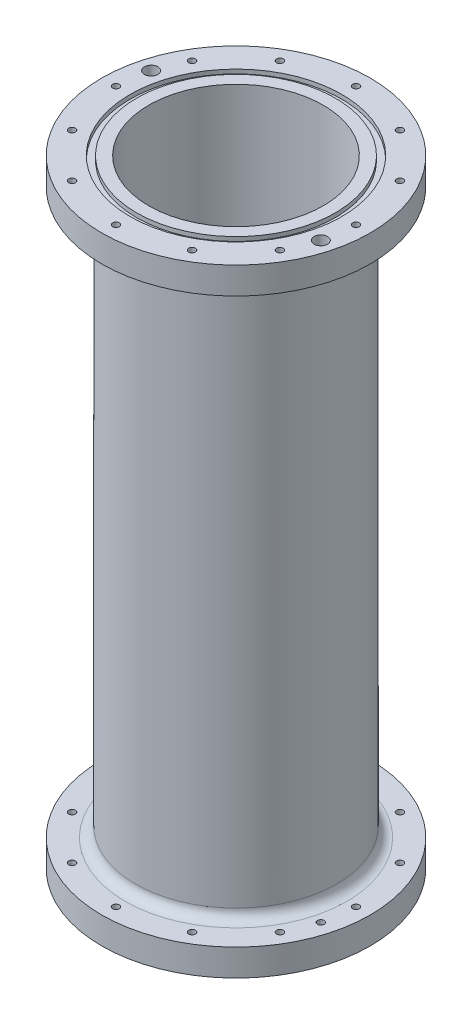
SolidWorks part; units mm, degrees
ref_plane "Front Plane" through (0, 0, 0) normal (0, 0, 1) x (1, 0, 0)
ref_plane "Top Plane" through (0, 0, 0) normal (0, 1, 0) x (1, 0, 0)
ref_plane "Right Plane" through (0, 0, 0) normal (1, 0, 0) x (0, 0, -1)
sketch "Sketch2" plane through (0, 0, 0) normal (0, 1, 0) x (1, 0, 0)
  circle A0 centre (0, 0) radius 41.275
  circle A1 centre (0, 0) radius 47.625
  dimension "D1" = 95.25
  dimension "D2" = 82.55
extrude "Base Cylinder" add sketch "Sketch2" along normal blind 292.1
sketch "Sketch3" plane through (0, 0, 0) normal (0, -1, 0) x (1, 0, 0)
  circle A0 centre (0, 0) radius 41.275
  circle A1 centre (0, 0) radius 63.5
  dimension "D1" = 127
extrude "Aft Flange" add sketch "Sketch3" against normal blind 12.7
sketch "Sketch4" plane through (0, 292.1, 0) normal (0, 1, 0) x (1, 0, 0)
  circle A0 centre (0, 0) radius 41.275
  circle A1 centre (0, 0) radius 63.5
  dimension "D1" = 127
extrude "Forward Flange" add sketch "Sketch4" against normal blind 12.7
sketch "Sketch6" plane through (0, 0, 0) normal (0, -1, 0) x (1, 0, 0)
  circle A0 centre (0, 0) radius 50.0761
  circle A1 centre (0, 0) radius 47.0027
  dimension "D1" = 100.1522
  dimension "D2" = 94.0054
extrude "Aft O-Ring" cut sketch "Sketch6" against normal blind 1.9812
sketch "Sketch7" plane through (0, 292.1, 0) normal (0, 1, 0) x (1, 0, 0)
  circle A0 centre (0, 0) radius 50.0761
  circle A1 centre (0, 0) radius 47.0027
  dimension "D1" = 100.1522
  dimension "D2" = 94.0054
extrude "Forward O-Ring" cut sketch "Sketch7" against normal blind 1.9812
sketch "Sketch For Bolt Holes" plane through (0, 0, 0) normal (0, -1, 0) x (1, 0, 0)
  circle A0 centre (-56.769, 0) radius 1.5875
  circle A1 centre (-49.1634, 28.3845) radius 1.5875
  circle A2 centre (-28.3845, 49.1634) radius 1.5875
  circle A3 centre (0, 56.769) radius 1.5875
  circle A4 centre (28.3845, 49.1634) radius 1.5875
  circle A5 centre (49.1634, 28.3845) radius 1.5875
  circle A6 centre (56.769, 0) radius 1.5875
  circle A7 centre (49.1634, -28.3845) radius 1.5875
  circle A8 centre (28.3845, -49.1634) radius 1.5875
  circle A9 centre (0, -56.769) radius 1.5875
  circle A10 centre (-28.3845, -49.1634) radius 1.5875
  circle A11 centre (-49.1634, -28.3845) radius 1.5875
  point P36 (0, 0)
  dimension "D2" = 3.175
  dimension "D1" = 56.769
  dimension "D3" = 12
hole_wizard "1/8 (0.125) Diameter Hole2" positions "Sketch8" profile "Sketch9" hole size "1/8" standard "ANSI Inch"
sketch "Sketch8" plane through (0, 0, 0) normal (0, -1, 0) x (-1, 0, 0)
  point P0 (-28.3845, -49.1634)
  point P3 (-49.1634, -28.3845)
  point P6 (-56.769, 0)
  point P9 (-49.1634, 28.3845)
  point P12 (-28.3845, 49.1634)
  point P15 (0, 56.769)
  point P18 (28.3845, 49.1634)
  point P21 (49.1634, 28.3845)
  point P24 (56.769, 0)
  point P27 (49.1634, -28.3845)
  point P30 (28.3845, -49.1634)
  point P33 (0, -56.769)
  point P36 (-28.3845, -49.1634)
  point P38 (-49.1634, -28.3845)
  point P40 (-56.769, 0)
sketch "Sketch9" plane through (28.3845, 0, 49.1634) normal (1, 0, 0) x (0, 0, -1)
  line L0 (0, 0) -> (0, 26.3539)
  line L1 (0, 26.3539) -> (1.5875, 25.4)
  line L2 (1.5875, 25.4) -> (1.5875, 0)
  line L5 (1.5875, 0) -> (0, 0)
  line L10 (0, 26.3539) -> (-1.5875, 25.4) construction
  line L11 (0, -6.35) -> (0, 107.95) construction
  dimension "Hole Dia." = 3.175
  dimension "Hole Depth" = 25.4
  dimension "Drill Angle" = 118
fillet "Flange Fillet" radius 4.7625 2 edges at (0, 12.7, -47.625) (0, 279.4, 47.625)
sketch "Dowel Hole Sketch" plane through (0, 0, 0) normal (0, -1, 0) x (1, 0, 0)
  line L0 (0, 0) -> (-56.769, 0) construction
  line L1 (0, 0) -> (-54.8346, -14.6929) construction
  line L2 (0, 0) -> (0, -56.769) construction
  line L3 (0, 0) -> (54.8346, 14.6929) construction
  circle A0 centre (0, 0) radius 56.769
  circle A1 centre (-54.8346, -14.6929) radius 4.6172
  circle A2 centre (54.8346, 14.6929) radius 3.4532
  dimension "D1" = 15
hole_wizard "1/4 (0.25) Press Dowel Hole1" positions "Sketch14" profile "Sketch12" hole size "1/4" standard "ANSI Inch"
sketch "Sketch14" plane through (0, 0, 0) normal (0, -1, 0) x (-1, 0, 0)
  point P0 (54.8346, 14.6929)
  point P3 (-54.8346, -14.6929)
sketch "Sketch12" plane through (-54.8346, 0, -14.6929) normal (1, 0, 0) x (0, 0, -1)
  line L0 (0, 0) -> (0, 8.2577)
  line L1 (0, 8.2577) -> (3.175, 6.35)
  line L2 (3.175, 6.35) -> (3.175, 0)
  line L5 (3.175, 0) -> (0, 0)
  line L10 (0, 8.2577) -> (-3.175, 6.35) construction
  line L11 (0, -6.35) -> (0, 107.95) construction
  dimension "Hole Dia." = 6.35
  dimension "Hole Depth" = 6.35
  dimension "Drill Angle" = 118
hole_wizard "1/8 (0.125) Diameter Hole4" positions "Sketch19" profile "Sketch21" hole size "1/8" standard "ANSI Inch" end condition up to next
sketch "Sketch19" plane through (0, 0, 0) normal (0, -1, 0) x (-1, 0, 0)
  point P0 (-54.8346, -14.6929)
  point P3 (54.8346, 14.6929)
sketch "Sketch21" plane through (54.8346, 0, 14.6929) normal (1, 0, 0) x (0, 0, -1)
  line L0 (0, 0) -> (0, 283.8423)
  line L1 (0, 283.8423) -> (1.5875, 283.8423)
  line L2 (1.5875, 283.8423) -> (1.5875, 0)
  line L5 (1.5875, 0) -> (0, 0)
  line L11 (0, -6.35) -> (0, 107.95) construction
  dimension "Thru Hole Dia." = 3.175
  dimension "Thru Hole Depth" = 283.8423
ref_plane "Hoop Mid-Plane" through (0, 146.05, 0) normal (0, 1, 0) x (1, 0, 0)
mirror "Forward Mirror BC and Pin" about plane through (0, 146.05, 0) normal (0, 1, 0) of "1/8 (0.125) Diameter Hole2", "1/8 (0.125) Diameter Hole4", "1/4 (0.25) Press Dowel Hole1"
